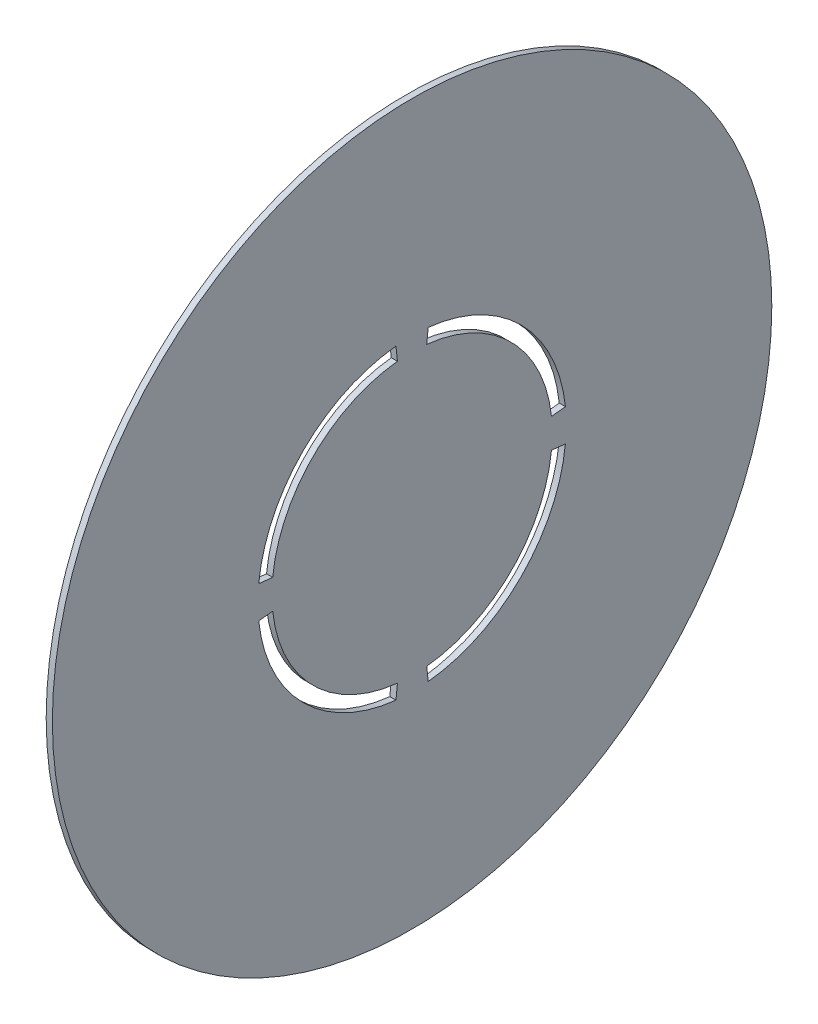
SolidWorks part; units mm, degrees
ref_plane "Front Plane" through (0, 0, 0) normal (0, 0, 1) x (1, 0, 0)
ref_plane "Top Plane" through (0, 0, 0) normal (0, 1, 0) x (1, 0, 0)
ref_plane "Right Plane" through (0, 0, 0) normal (1, 0, 0) x (0, 0, -1)
sketch "Sketch1" plane through (0, 0, 0) normal (1, 0, 0) x (0, 0, -1)
  circle A0 centre (0, 0) radius 48.895
  circle A1 centre (0, 0) radius 20.955
  dimension "D1" = 97.79
  dimension "D2" = 41.91
extrude "Boss-Extrude1" add sketch "Sketch1" along normal blind 0.8382
sketch "Sketch2" plane through (0, 0, 0) normal (1, 0, 0) x (0, 0, -1)
  line L0 (0, 19.05) -> (0, 20.955) construction
  line L1 (-2.1904, 20.8402) -> (-1.9913, 18.9456)
  line L2 (2.1904, 20.8402) -> (1.9913, 18.9456)
  line L3 (20.8402, 2.1904) -> (18.9456, 1.9913)
  line L4 (20.8402, -2.1904) -> (18.9456, -1.9913)
  line L5 (19.05, 0) -> (20.955, 0) construction
  line L6 (2.1904, -20.8402) -> (1.9913, -18.9456)
  line L7 (-2.1904, -20.8402) -> (-1.9913, -18.9456)
  line L8 (0, -19.05) -> (0, -20.955) construction
  line L9 (-20.8402, -2.1904) -> (-18.9456, -1.9913)
  line L10 (-20.8402, 2.1904) -> (-18.9456, 1.9913)
  line L11 (-19.05, 0) -> (-20.955, 0) construction
  circle A1 centre (0, 0) radius 20.955 construction
  arc A2 (-2.1904, 20.8402) -> (2.1904, 20.8402) centre (0, 0) cw
  arc A3 (20.8402, 2.1904) -> (20.8402, -2.1904) centre (0, 0) cw
  arc A4 (1.9913, 18.9456) -> (18.9456, 1.9913) centre (0, 0) cw
  arc A5 (2.1904, -20.8402) -> (-2.1904, -20.8402) centre (0, 0) cw
  arc A6 (18.9456, -1.9913) -> (1.9913, -18.9456) centre (0, 0) cw
  arc A7 (-20.8402, -2.1904) -> (-20.8402, 2.1904) centre (0, 0) cw
  arc A8 (-1.9913, -18.9456) -> (-18.9456, -1.9913) centre (0, 0) cw
  arc A9 (-18.9456, 1.9913) -> (-1.9913, 18.9456) centre (0, 0) cw
  point P35 (0, 0)
  dimension "D1" = 6
  dimension "D4" = 19.05
  dimension "D2" = 6
  dimension "D3" = 4
extrude "Boss-Extrude2" add sketch "Sketch2" along normal blind 0.8382
